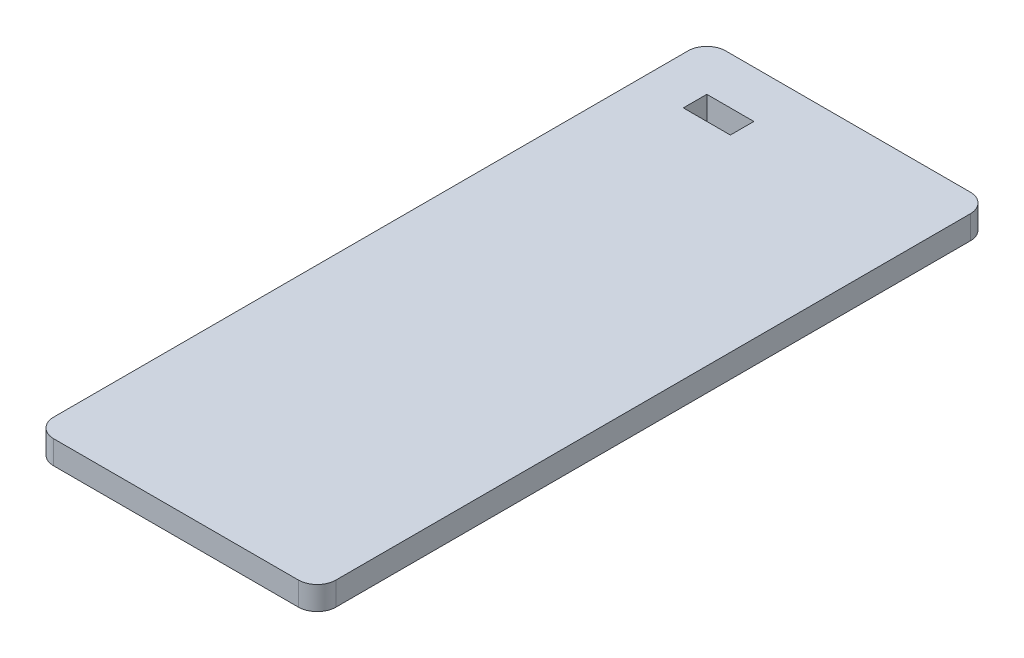
SolidWorks part; units mm, degrees
material "Acrylic (Medium-high impact)"
ref_plane "Front Plane" through (0, 0, 0) normal (0, 0, 1) x (1, 0, 0)
ref_plane "Top Plane" through (0, 0, 0) normal (0, 1, 0) x (1, 0, 0)
ref_plane "Right Plane" through (0, 0, 0) normal (1, 0, 0) x (0, 0, -1)
ref_plane "Plane1" through (0, 0, 0) normal (0, 1, 0) x (1, 0, 0)
sketch "Sketch1" plane through (0, 0, 0) normal (0, 1, 0) x (1, 0, 0)
  line L1 (0, 0) -> (38.1, 0)
  line L2 (0, 0) -> (0, 90.7)
  line L3 (0, 90.7) -> (38.1, 90.7)
  line L4 (38.1, 0) -> (38.1, 90.7)
  dimension "D1" = 38.1
  dimension "D2" = 90.7
extrude "Boss-Extrude1" add sketch "Sketch1" along normal blind 3.175
sketch "Sketch2" plane through (0, 3.175, 0) normal (0, 1, 0) x (1, 0, 0)
  line L1 (6.35, 84.35) -> (12.7, 84.35)
  line L2 (6.35, 84.35) -> (6.35, 81.175)
  line L3 (6.35, 81.175) -> (12.7, 81.175)
  line L4 (12.7, 84.35) -> (12.7, 81.175)
  line L6 (38.1, 90.7) -> (0, 90.7) construction
  line L7 (0, 90.7) -> (0, 0) construction
  point P10 (50.6432, 76.9324)
  dimension "D1" = 3.175
  dimension "D2" = 6.35
  dimension "D3" = 6.35
  dimension "D4" = 6.35
extrude "Cut-Extrude1" cut sketch "Sketch2" against normal through all
fillet "Fillet1" radius 2.54 4 edges at (38.1, 1.5875, 0) (0, 1.5875, 0) (38.1, 1.5875, -90.7) (0, 1.5875, -90.7)
